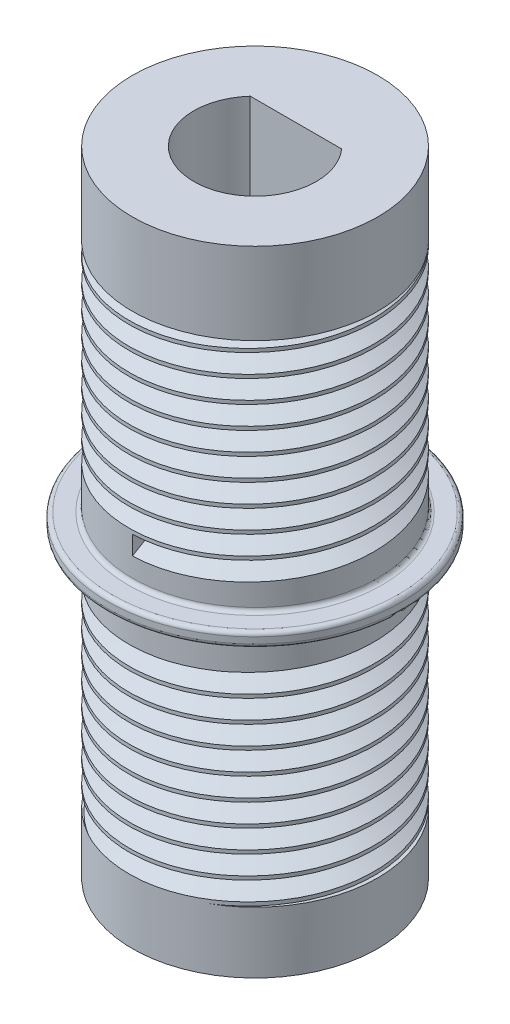
SolidWorks part; units mm, degrees
ref_plane "Front Plane" through (0, 0, 0) normal (0, 0, 1) x (1, 0, 0)
ref_plane "Top Plane" through (0, 0, 0) normal (0, 1, 0) x (1, 0, 0)
ref_plane "Right Plane" through (0, 0, 0) normal (1, 0, 0) x (0, 0, -1)
sketch "Sketch1" plane through (0, 0, 0) normal (0, 1, 0) x (1, 0, 0)
  circle A2 centre (0, 0) radius 3
  dimension "D1" = 6
extrude "Boss-Extrude2" add sketch "Sketch1" along normal blind 12 contours A2
sketch "Sketch8" plane through (0, 0, 0) normal (0, -1, 0) x (1, 0, 0)
  circle A0 centre (0, 0) radius 3
  dimension "D1" = 6
curve "Helix/Spiral2" pitch 0.55 height 4.95 radius 3 centre (0, 0, 0) axis (0, 1, 0) start towards (0, 0, -1)
sketch "Sketch13" plane through (0, 0, 0) normal (1, 0, 0) x (0, 0, -1)
  line L1 (2.6, 0) -> (3.2, -0.3464)
  line L2 (3.2, -0.3464) -> (3.2, 0.3464)
  line L3 (3.2, 0.3464) -> (2.6, 0)
  line L5 (-3, 0) -> (3, 0) construction
  circle A0 centre (3, 0) radius 0.2 construction
  dimension "D1" = 0.4
sweep "Cut-Sweep1" cut profiles "Sketch13" path "Helix/Spiral2" align with end faces yes
sketch "Sketch16" plane through (0, 12, 0) normal (0, 1, 0) x (1, 0, 0)
  circle A0 centre (0, 0) radius 3
  dimension "D1" = 6
curve "Helix/Spiral3" pitch 0.55 height 4.95 radius 3 centre (0, 12, 0) axis (0, -1, 0) start towards (0, 0, 1)
sketch "Sketch17" plane through (0, 0, 0) normal (1, 0, 0) x (0, 0, -1)
  line L0 (3, 12) -> (-3, 12) construction
  line L1 (-2.6, 12) -> (-3.2, 12.3464)
  line L2 (-3.2, 12.3464) -> (-3.2, 11.6536)
  line L3 (-3.2, 11.6536) -> (-2.6, 12)
  circle A0 centre (-3, 12) radius 0.2 construction
  point P1 (0, 0)
  dimension "D1" = 0.4
sweep "Cut-Sweep2" cut profiles "Sketch17" path "Helix/Spiral3" align with end faces yes
sketch "Sketch18" plane through (0, 0, 0) normal (0, -1, 0) x (1, 0, 0)
  circle A0 centre (0, 0) radius 3
extrude "Boss-Extrude3" add sketch "Sketch18" along normal blind 1.5
sketch "Sketch21" plane through (0, 12, 0) normal (0, 1, 0) x (1, 0, 0)
  circle A0 centre (0, 0) radius 3
  dimension "D1" = 6
extrude "Boss-Extrude5" add sketch "Sketch21" along normal blind 2
sketch "Sketch22" plane through (0, 14, 0) normal (0, 1, 0) x (1, 0, 0)
  line L0 (0, 0) -> (0, 1)
  line L1 (1.118, 1) -> (-1.118, 1)
  arc A0 (-1.118, 1) -> (1.118, 1) centre (0, 0) ccw
  point P7 (0, 1)
  dimension "D1" = 3
  dimension "D2" = 1
ref_plane "Plane2" through (0, 5.1809, -3) normal (0, 1, 0) x (1, 0, 0)
extrude "Cut-Extrude8" cut sketch "Sketch22" against normal blind 10 contours L1 A0 region at (0, 14, 0.148)
ref_plane "Plane3" through (0, 6.25, 0) normal (0, -1, 0) x (-1, 0, 0)
sketch "Sketch32" plane through (0, 6.25, 0) normal (0, -1, 0) x (-1, 0, 0)
  circle A0 centre (0, 0) radius 3.6
  dimension "D1" = 7.2
extrude "Boss-Extrude6" add sketch "Sketch32" along normal blind 0.35
fillet "Fillet1" radius 0.1 4 edges at (0, 6.25, -3) (0, 5.9, -3) (0, 5.9, -3.6) (0, 6.25, -3.6)
